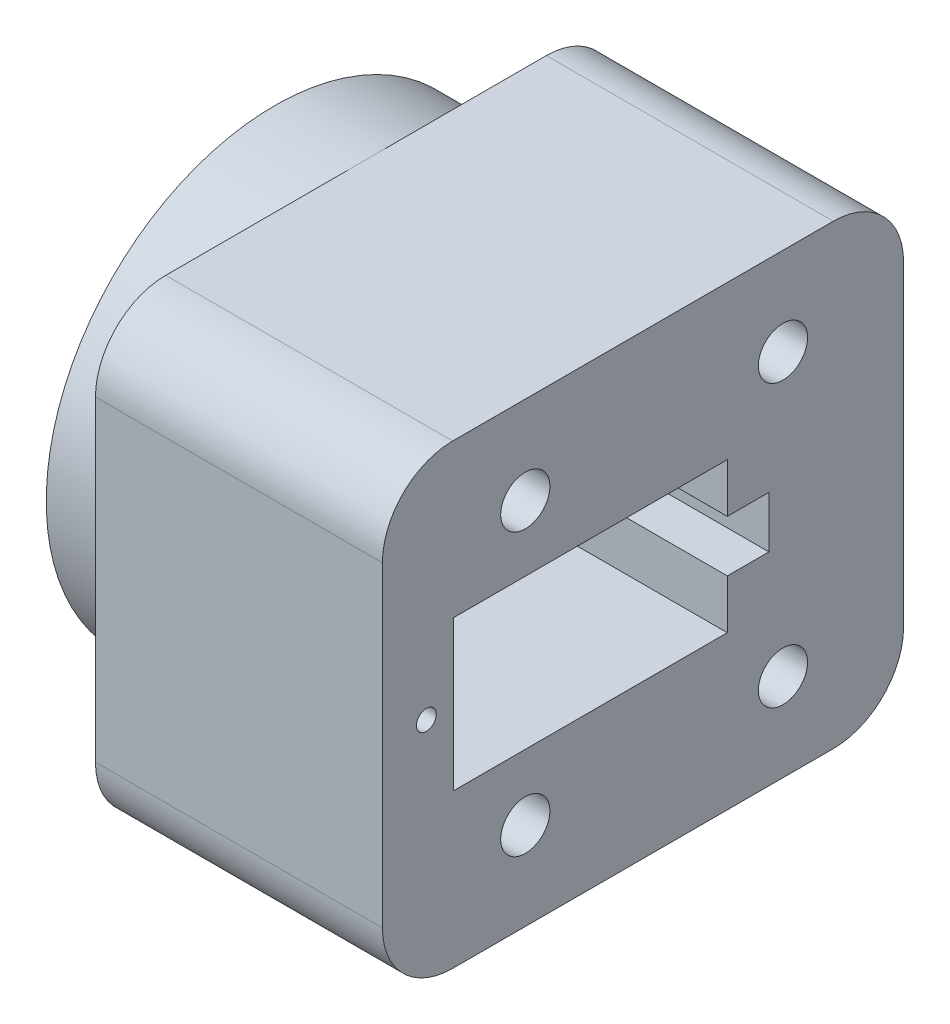
SolidWorks part; units mm, degrees
ref_plane "Front Plane" through (0, 0, 0) normal (0, 0, 1) x (1, 0, 0)
ref_plane "Top Plane" through (0, 0, 0) normal (0, 1, 0) x (1, 0, 0)
ref_plane "Right Plane" through (0, 0, 0) normal (1, 0, 0) x (0, 0, -1)
ref_plane "Plane1" through (169.4, 0, 0) normal (1, 0, 0) x (0, 0, -1)
sketch "Sketch1" plane through (169.4, 0, 0) normal (1, 0, 0) x (0, 0, -1)
  line L1 (-324.2, -8.5) -> (-283.5, -8.5)
  line L2 (-324.2, -8.5) -> (-324.2, 8.5)
  line L3 (-324.2, 8.5) -> (-283.5, 8.5)
  line L4 (-283.5, -8.5) -> (-283.5, 8.5)
extrude "Boss-Extrude1" add sketch "Sketch1" along normal blind 24.5
ref_plane "Plane2" through (189.9, 0, 0) normal (1, 0, 0) x (0, 0, -1)
sketch "Sketch2" plane through (189.9, 0, 0) normal (1, 0, 0) x (0, 0, -1)
  line L1 (-324.2, -17) -> (-283.5, -17)
  line L2 (-324.2, -17) -> (-324.2, 17)
  line L3 (-324.2, 17) -> (-283.5, 17)
  line L4 (-283.5, -17) -> (-283.5, 17)
extrude "Boss-Extrude2" add sketch "Sketch2" along normal blind 4
sketch "Sketch3" plane through (169.4, 0, 0) normal (1, 0, 0) x (0, 0, -1)
  circle A0 centre (-301, 0) radius 3.6
extrude "Cut-Extrude1" cut sketch "Sketch3" along normal blind 4.4
sketch "Sketch4" plane through (169.4, 0, 0) normal (1, 0, 0) x (0, 0, -1)
  line L0 (-285.15, -1.95) -> (-301, -2.8)
  line L1 (-301, -2.8) -> (-316.85, -1.95)
  line L2 (-316.85, -1.95) -> (-316.85, 1.95)
  line L3 (-316.85, 1.95) -> (-301, 2.8)
  line L4 (-301, 2.8) -> (-285.15, 1.95)
  line L5 (-285.15, 1.95) -> (-285.15, -1.95)
extrude "Cut-Extrude2" cut sketch "Sketch4" along normal blind 4.4
sketch "Sketch5" plane through (169.4, 0, 0) normal (1, 0, 0) x (0, 0, -1)
  circle A0 centre (-301, 0) radius 1.2
extrude "Cut-Extrude3" cut sketch "Sketch5" along normal blind 7
ref_plane "Plane3" through (194.5, 0, 0) normal (1, 0, 0) x (0, 0, -1)
sketch "Sketch6" plane through (194.5, 0, 0) normal (1, 0, 0) x (0, 0, -1)
  line L1 (-318.15, -6.4) -> (-294.75, -6.4)
  line L2 (-318.15, -6.4) -> (-318.15, 6.4)
  line L3 (-318.15, 6.4) -> (-294.75, 6.4)
  line L4 (-294.75, -6.4) -> (-294.75, 6.4)
extrude "Cut-Extrude4" cut sketch "Sketch6" against normal blind 19.2
sketch "Sketch7" plane through (194.5, 0, 0) normal (1, 0, 0) x (0, 0, -1)
  line L1 (-294.9, -2.2) -> (-291.2, -2.2)
  line L2 (-294.9, -2.2) -> (-294.9, 2.2)
  line L3 (-294.9, 2.2) -> (-291.2, 2.2)
  line L4 (-291.2, -2.2) -> (-291.2, 2.2)
extrude "Cut-Extrude5" cut sketch "Sketch7" against normal blind 16
sketch "Sketch8" plane through (194.5, 0, 0) normal (1, 0, 0) x (0, 0, -1)
  circle A0 centre (-320.45, 0) radius 0.85
extrude "Cut-Extrude6" cut sketch "Sketch8" against normal blind 8.6
sketch "Sketch9" plane through (194.5, 0, 0) normal (1, 0, 0) x (0, 0, -1)
  circle A0 centre (-290, 12) radius 1.7
  circle A1 centre (-290, -12) radius 1.7
  circle A2 centre (-312, 12) radius 1.7
  circle A3 centre (-312, -12) radius 1.7
extrude "Cut-Extrude7" cut sketch "Sketch9" against normal blind 4.7
ref_plane "Plane4" through (0, 0, 283) normal (0, 0, 1) x (1, 0, 0)
sketch "Sketch10" plane through (0, 0, 283) normal (0, 0, 1) x (1, 0, 0)
  line L1 (178.5, -2.2) -> (184, -2.2)
  line L2 (178.5, -2.2) -> (178.5, 2.2)
  line L3 (178.5, 2.2) -> (184, 2.2)
  line L4 (184, -2.2) -> (184, 2.2)
extrude "Cut-Extrude8" cut sketch "Sketch10" along normal blind 8.3
sketch "Sketch11" plane through (169.4, 0, 0) normal (1, 0, 0) x (0, 0, -1)
  line L0 (-279.7, -19.5) -> (-324.2, -19.5)
  line L1 (-324.2, -19.5) -> (-324.2, -8.5)
  line L2 (-324.2, -8.5) -> (-283.5, -8.5)
  line L3 (-283.5, -8.5) -> (-283.5, 8.5)
  line L4 (-283.5, 8.5) -> (-324.2, 8.5)
  line L5 (-324.2, 8.5) -> (-324.2, 19.5)
  line L6 (-324.2, 19.5) -> (-279.7, 19.5)
  line L7 (-279.7, 19.5) -> (-279.7, -19.5)
extrude "Boss-Extrude3" add sketch "Sketch11" along normal blind 24.5
sketch "Sketch12" plane through (0, 0, 283) normal (0, 0, 1) x (1, 0, 0)
  line L1 (178.5, -2.2) -> (184, -2.2)
  line L2 (178.5, -2.2) -> (178.5, 2.2)
  line L3 (178.5, 2.2) -> (184, 2.2)
  line L4 (184, -2.2) -> (184, 2.2)
extrude "Cut-Extrude9" cut sketch "Sketch12" along normal mid plane 7
sketch "Sketch13" plane through (169.4, 0, 0) normal (1, 0, 0) x (0, 0, -1)
  line L0 (-324.2, 13.5) -> (-325.5, 13.5)
  line L1 (-325.5, 13.5) -> (-325.5, 20.5)
  line L2 (-325.5, 20.5) -> (-318.2, 20.5)
  line L3 (-318.2, 20.5) -> (-318.2, 19.5)
  line L4 (-324.2, -13.5) -> (-325.5, -13.5)
  line L5 (-325.5, -13.5) -> (-325.5, -20.5)
  line L6 (-325.5, -20.5) -> (-318.2, -20.5)
  line L7 (-318.2, -20.5) -> (-318.2, -19.5)
  line L8 (-279.7, 13.5) -> (-278.4, 13.5)
  line L9 (-278.4, 13.5) -> (-278.4, 20.5)
  line L10 (-278.4, 20.5) -> (-285.7, 20.5)
  line L11 (-285.7, 20.5) -> (-285.7, 19.5)
  line L12 (-279.7, -13.5) -> (-278.4, -13.5)
  line L13 (-278.4, -13.5) -> (-278.4, -20.5)
  line L14 (-278.4, -20.5) -> (-285.7, -20.5)
  line L15 (-285.7, -20.5) -> (-285.7, -19.5)
  arc A0 (-318.2, 19.5) -> (-324.2, 13.5) centre (-318.2, 13.5) ccw
  arc A1 (-318.2, -19.5) -> (-324.2, -13.5) centre (-318.2, -13.5) cw
  arc A2 (-285.7, 19.5) -> (-279.7, 13.5) centre (-285.7, 13.5) cw
  arc A3 (-285.7, -19.5) -> (-279.7, -13.5) centre (-285.7, -13.5) ccw
extrude "Cut-Extrude10" cut sketch "Sketch13" along normal through all
sketch "Sketch14" plane through (169.4, 0, 0) normal (1, 0, 0) x (0, 0, -1)
  circle A0 centre (-301, 0) radius 19.5
  circle A1 centre (-301, 0) radius 18.3
extrude "Boss-Extrude4" add sketch "Sketch14" against normal blind 7.9
sketch "Sketch15" plane through (194.5, 0, 0) normal (1, 0, 0) x (0, 0, -1)
  circle A0 centre (-290, 12) radius 2.1
  circle A1 centre (-290, -12) radius 2.1
  circle A2 centre (-312, 12) radius 2.1
  circle A3 centre (-312, -12) radius 2.1
extrude "Cut-Extrude11" cut sketch "Sketch15" against normal blind 6.1
